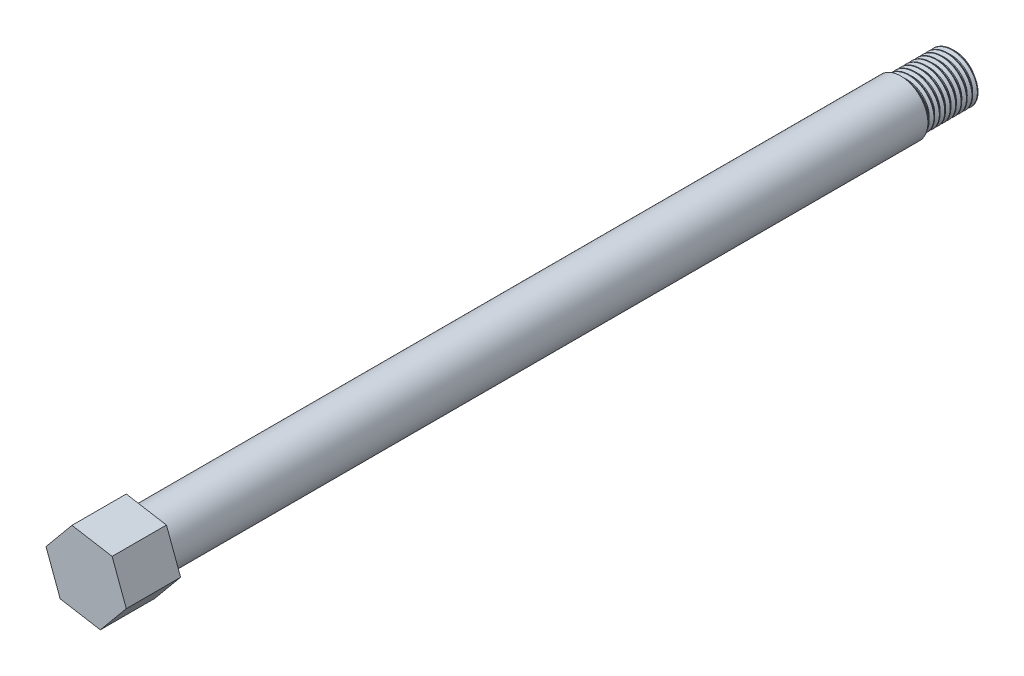
SolidWorks part; units mm, degrees
ref_plane "Front Plane" through (0, 0, 0) normal (0, 0, 1) x (1, 0, 0)
ref_plane "Top Plane" through (0, 0, 0) normal (0, 1, 0) x (1, 0, 0)
ref_plane "Right Plane" through (0, 0, 0) normal (1, 0, 0) x (0, 0, -1)
sketch "Sketch1" plane through (0, 0, 0) normal (0, 0, 1) x (1, 0, 0)
  line L1 (-4.7833, -5.7766) -> (2.6111, -7.0308)
  line L2 (2.6111, -7.0308) -> (7.3944, -1.2542)
  line L3 (7.3944, -1.2542) -> (4.7833, 5.7766)
  line L4 (4.7833, 5.7766) -> (-2.6111, 7.0308)
  line L5 (-2.6111, 7.0308) -> (-7.3944, 1.2542)
  line L6 (-7.3944, 1.2542) -> (-4.7833, -5.7766)
  circle A2 centre (0, 0) radius 6.4952 construction
extrude "Boss-Extrude1" add sketch "Sketch1" along normal blind 10
sketch "Sketch2" plane through (0, 0, 0) normal (0, 0, -1) x (-1, 0, 0)
  circle A0 centre (0, 0) radius 5
  dimension "D1" = 10
extrude "Boss-Extrude2" add sketch "Sketch2" along normal blind 150
sketch "Sketch4" plane through (0, 0, -150) normal (0, 0, -1) x (-1, 0, 0)
  circle A0 centre (0, 0) radius 4
  dimension "D1" = 8
extrude "Cut-Extrude1" cut sketch "Sketch4" against normal blind 10 flip side to cut
thread "Thread1" pitch 1 method extrude profile "Thread Profile2" start angle 0, offset 1, length 11, pitch 1, diameter 8
ref_plane "Plane3" through (4, 0, -151) normal (0, -1, 0) x (1, 0, 0)
sketch "Thread Profile2" plane through (4, 0, -151) normal (0, -1, 0) x (1, 0, 0)
  line L0 (0, 0) -> (0, 1) construction
  line L1 (0, 0) -> (0.5413, 0.3125)
  line L2 (0.5413, 0.3125) -> (0.5413, 0.4375)
  line L3 (0.5413, 0.4375) -> (0, 0.75)
  line L4 (0.5413, 0.375) -> (0, 0.375) construction
  line L11 (0, 0) -> (0, 0.75)
  point P2 (0, 0)
  dimension "Pitch" = 1
  dimension "Profile_Angle" = 60
  dimension "Profile_Land" = 0.125
  dimension "Profile_Height" = 0.5413
sketch "Sketch18" plane through (0, 0, -150) normal (0, 0, -1) x (-1, 0, 0)
  circle A0 centre (0, 0) radius 7.5
  dimension "D1" = 15
extrude "Cut-Extrude2" cut sketch "Sketch18" along normal blind 10
